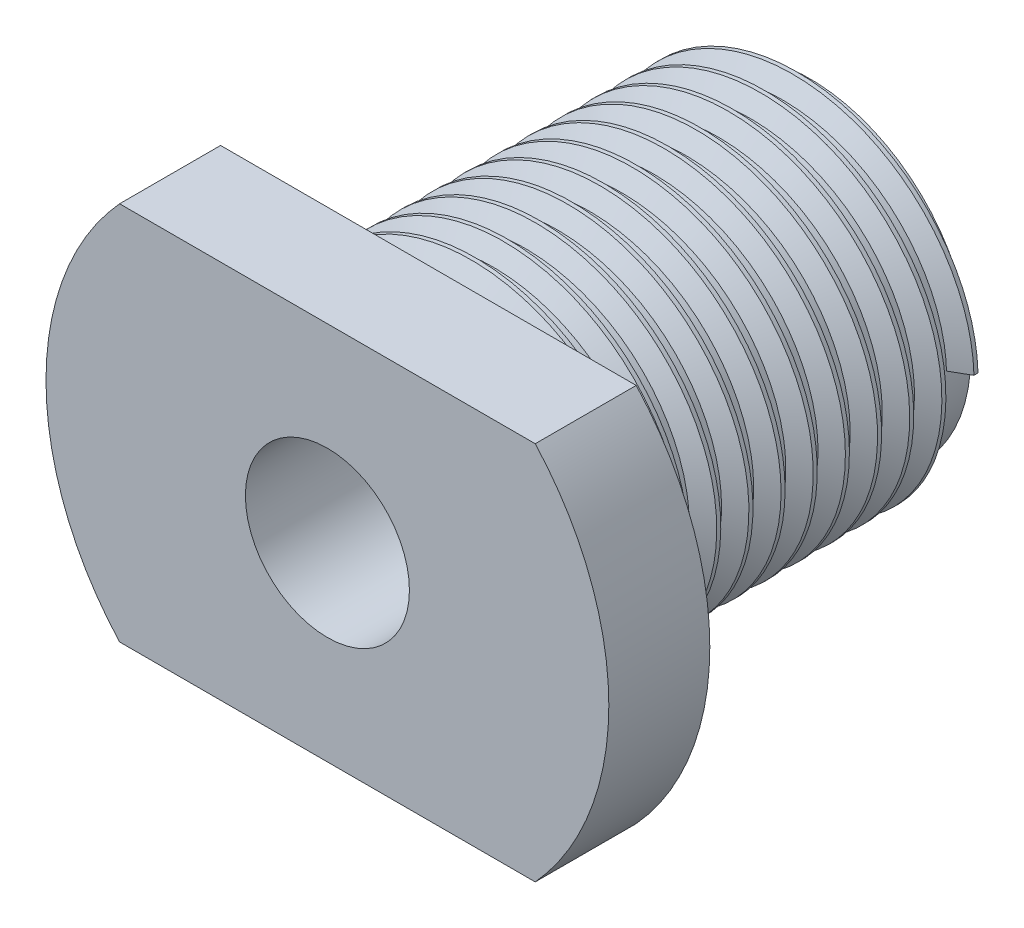
SolidWorks part; units mm, degrees
ref_plane "Front Plane" through (0, 0, 0) normal (0, 0, 1) x (1, 0, 0)
ref_plane "Top Plane" through (0, 0, 0) normal (0, 1, 0) x (1, 0, 0)
ref_plane "Right Plane" through (0, 0, 0) normal (1, 0, 0) x (0, 0, -1)
sketch "Sketch2" plane through (0, 0, 0) normal (0, 0, 1) x (1, 0, 0)
  line L0 (-8.2063, 7.493) -> (8.2063, 7.493)
  line L1 (-14.8755, 0) -> (17.2821, 0) construction
  line L2 (-8.2063, -7.493) -> (8.2063, -7.493)
  arc A0 (-8.2063, 7.493) -> (-8.2063, -7.493) centre (0, 0) ccw
  arc A1 (8.2063, -7.493) -> (8.2063, 7.493) centre (0, 0) ccw
  dimension "D1" = 22.225
  dimension "D2" = 7.493
extrude "Boss-Extrude1" add sketch "Sketch2" along normal blind 3.9878
sketch "Sketch3" plane through (0, 0, 0) normal (0, 0, -1) x (-1, 0, 0)
  circle A0 centre (0, 0) radius 6.35
extrude "Boss-Extrude2" add sketch "Sketch3" along normal blind 15.0622
thread "Thread1" pitch 1.27 method extrude profile "Thread Profile1" start angle 0, offset 0, length 0, pitch 1.27, diameter 12.7
ref_plane "Plane1" through (6.35, 0, -15.0622) normal (0, -1, 0) x (1, 0, 0)
sketch "Thread Profile1" plane through (6.35, 0, -15.0622) normal (0, -1, 0) x (1, 0, 0)
  line L0 (0, 0) -> (0, 1.27) construction
  line L1 (0, 0) -> (0.6874, 0.3969)
  line L2 (0.6874, 0.3969) -> (0.6874, 0.5556)
  line L3 (0.6874, 0.5556) -> (0, 0.9525)
  line L4 (0.6874, 0.4762) -> (0, 0.4762) construction
  line L11 (0, 0) -> (0, 0.9525)
  point P2 (0, 0)
  dimension "Pitch" = 1.27
  dimension "Profile_Angle" = 60
  dimension "Profile_Land" = 0.1588
  dimension "Profile_Height" = 0.6874
hole_wizard "CSK for 1/4 Flat Head Machine Screw (100)1" positions "Sketch9" profile "Sketch10" countersink size "1/4" standard "ANSI Inch" end condition up to next
sketch "Sketch9" plane through (0, 0, -15.0622) normal (0, 0, -1) x (-1, 0, 0)
  point P0 (0, 0)
sketch "Sketch10" plane through (0, 0, -15.0622) normal (1, 0, 0) x (0, 1, 0)
  line L0 (0, 0) -> (0, 19.05)
  line L1 (0, 19.05) -> (3.2385, 19.05)
  line L2 (3.2385, 19.05) -> (3.2385, 1.9448)
  line L3 (3.2385, 1.9448) -> (5.5562, 0)
  line L5 (5.5562, 0) -> (0, 0)
  line L6 (-3.2385, 1.9448) -> (-5.5562, 0) construction
  line L11 (0, -6.35) -> (0, 107.95) construction
  dimension "Thru Hole Dia." = 6.477
  dimension "Thru Hole Depth" = 19.05
  dimension "Near C'Sink Dia." = 11.1125
  dimension "Near C'Sink Angle" = 100
